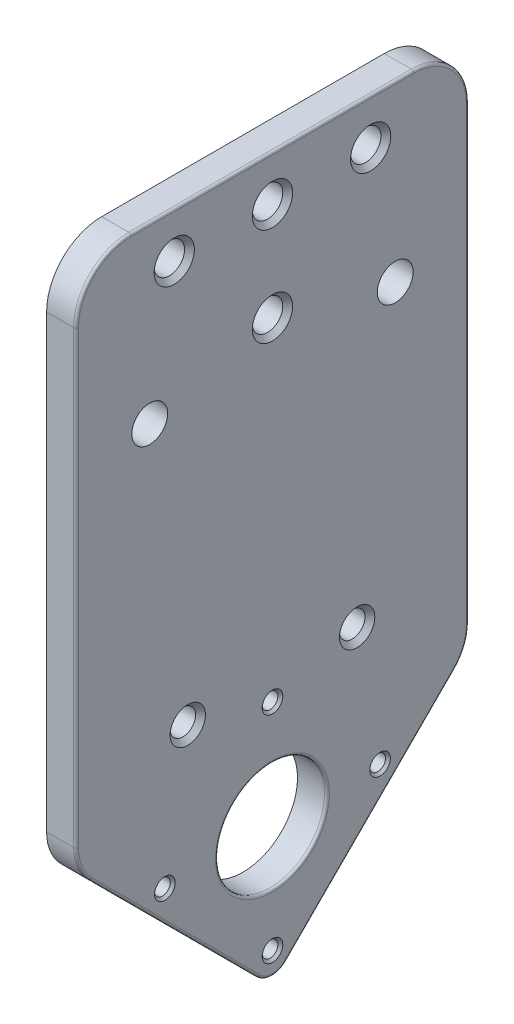
SolidWorks part; units mm, degrees
ref_plane "Спереди (Плоскость XY)" through (0, 0, 0) normal (0, 0, 1) x (1, 0, 0)
ref_plane "Сверху (Плоскость XZ)" through (0, 0, 0) normal (0, 1, 0) x (1, 0, 0)
ref_plane "Справа (Плоскость ZY)" through (0, 0, 0) normal (1, 0, 0) x (0, 0, -1)
sketch "Эскиз2" plane through (0, 0, 0) normal (1, 0, 0) x (0, 0, -1)
  line L0 (-10.5518, -35.8284) -> (10.5656, -56.9458) construction
  line L1 (11.8795, -34.5145) -> (-11.8657, -58.2597) construction
  line L2 (-5.8996, -46.3871) -> (5.818, -46.3871) construction
  line L3 (0, -168.396) -> (0, 124.0583) construction
  line L4 (-28.7833, 72.5422) -> (28.7833, 72.5422)
  line L5 (37.0711, -37.4625) -> (2.8284, -71.7051)
  line L6 (40, 61.3255) -> (40, -30.3914)
  line L141 (-40, 61.3255) -> (-40, -30.3914)
  line L142 (-37.0711, -37.4625) -> (-2.8284, -71.7051)
  circle A1 centre (-21.9134, -46.3871) radius 1.6
  circle A4 centre (17.25, -19.8871) radius 2.6
  circle A5 centre (-17.25, -19.8871) radius 2.6
  circle A6 centre (0.0069, -46.3871) radius 11.1
  circle A7 centre (-25, 37.1129) radius 3.655
  circle A8 centre (-20, 63.3206) radius 3.1
  circle A9 centre (0, 63.3206) radius 3.1
  circle A10 centre (0, 43.3206) radius 3.1
  circle A11 centre (20, 63.3206) radius 3.1
  circle A12 centre (25, 37.1129) radius 3.655
  circle A13 centre (0.0069, -24.4668) radius 1.6
  circle A14 centre (21.9272, -46.3871) radius 1.6
  circle A15 centre (0.0069, -68.3074) radius 1.6
  arc A18 (-40, 61.3255) -> (-28.7833, 72.5422) centre (-28.7833, 61.3255) cw
  arc A19 (40, 61.3255) -> (28.7833, 72.5422) centre (28.7833, 61.3255) ccw
  arc A20 (37.0711, -37.4625) -> (40, -30.3914) centre (30, -30.3914) ccw
  arc A21 (-40, -30.3914) -> (-37.0711, -37.4625) centre (-30, -30.3914) ccw
  arc A22 (-2.8284, -71.7051) -> (2.8284, -71.7051) centre (0, -68.8767) ccw
  point P0 (-20, 63.3206)
  point P1 (0, 63.3206)
  point P2 (20, 63.3206)
  point P3 (0, 43.3206)
  point P4 (-25, 37.1129)
  point P5 (-17.25, -19.8871)
  point P7 (17.25, -19.8871)
  point P9 (-21.9134, -46.3871)
  point P11 (0.0069, -46.3871)
  point P12 (25, 37.1129)
  point P43 (0.0069, -46.3871)
  point P55 (0, 72.5422)
  point P63 (40, -34.5335)
  point P66 (-40, -34.5335)
  dimension "D1" = 22.2
  dimension "D2" = 3.2
  dimension "D3" = 5.2
  dimension "D4" = 6.2
  dimension "D10" = 57
  dimension "D18" = 7.31
  dimension "D19" = 90
  dimension "D20" = 10
  dimension "D15" = 4
  dimension "D5" = 31
  dimension "D6" = 90
  dimension "D7" = 45
  dimension "D8" = 31
  dimension "D11" = 26.5
  dimension "D12" = 20
  dimension "D13" = 34.5
  dimension "D14" = 50
  dimension "D16" = 40
  dimension "D17" = 80
  dimension "D9" = 4
extrude "Бобышка-Вытянуть1" add sketch "Эскиз2" along normal blind 6
chamfer "Фаска1" distance 1 angle 45 6 edges at (6, 63.3206, -23.1) (6, 63.3206, 16.9) (6, 63.3206, -3.1) (6, 43.3206, -3.1) (6, -19.8871, 14.65) (6, -19.8871, -19.85)
chamfer "Фаска2" distance 0.5 angle 45 4 edges at (6, -68.3074, -1.6069) (6, -46.3871, -23.5272) (6, -46.3871, 20.3134) (6, -24.4668, -1.6069)
fillet "Скругление1" radius 0.5 11 edges at (6, 69.2569, -36.7147) (6, 15.4671, -40) (6, -34.2182, -39.2388) (6, -54.5838, -19.9497) (6, -72.8767, 0) (6, -54.5838, 19.9497) (6, -34.2182, 39.2388) (6, 15.4671, 40) (6, 69.2569, 36.7147) (6, 72.5422, 0) (6, -46.3871, -11.1069)
equation "\"deltahole\"= 0.4"
